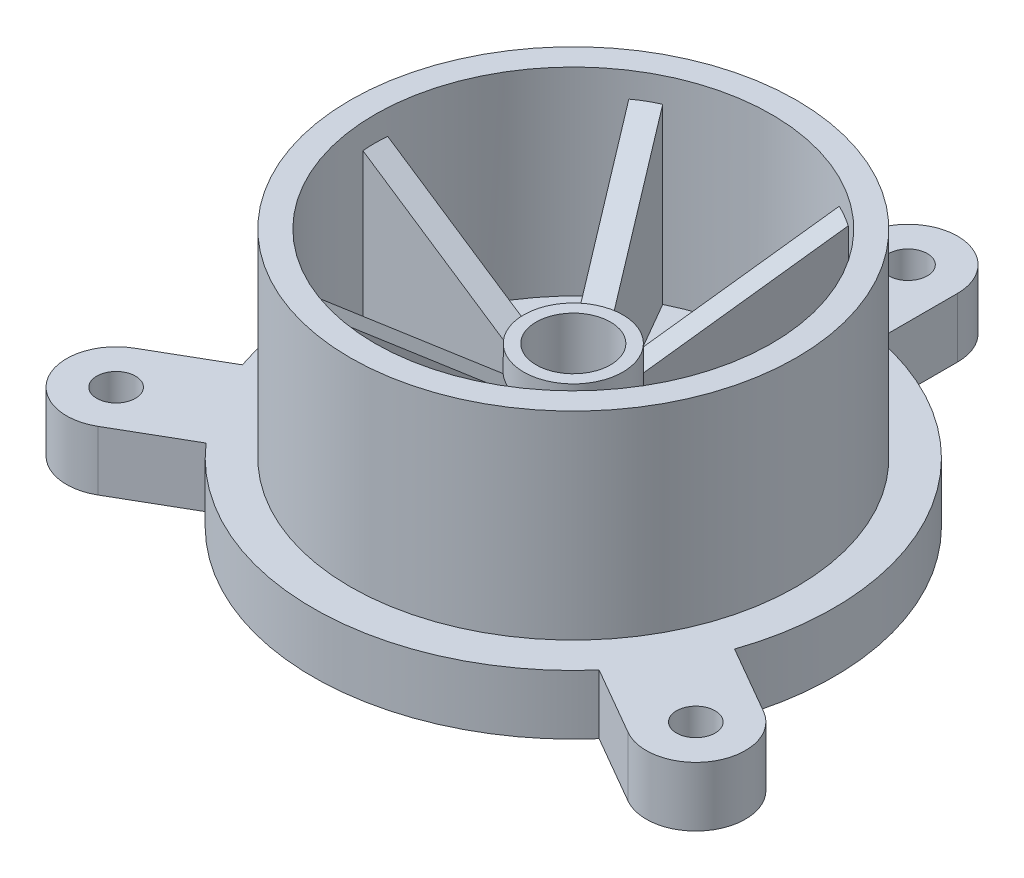
SolidWorks part; units mm, degrees
ref_plane "Front Plane" through (0, 0, 0) normal (0, 0, 1) x (1, 0, 0)
ref_plane "Top Plane" through (0, 0, 0) normal (0, 1, 0) x (1, 0, 0)
ref_plane "Right Plane" through (0, 0, 0) normal (1, 0, 0) x (0, 0, -1)
sketch "Sketch1" plane through (0, 0, 0) normal (0, 1, 0) x (1, 0, 0)
  line L0 (-10, 67.5) -> (-10, 51.5388)
  line L1 (10, 67.5) -> (10, 51.5388)
  line L2 (63.4567, -25.0897) -> (49.6339, -17.1092)
  line L3 (53.4567, -42.4103) -> (39.6339, -34.4297)
  line L4 (-53.4567, -42.4103) -> (-39.6339, -34.4297)
  line L5 (-63.4567, -25.0897) -> (-49.6339, -17.1092)
  arc A0 (-10, 51.5388) -> (-49.6339, -17.1092) centre (0, 0) ccw
  circle A1 centre (0, 0) radius 67.5 construction
  circle A2 centre (0, 67.5) radius 3.9
  arc A3 (9.9725, 66.7593) -> (-9.9725, 66.7593) centre (0, 67.5) ccw
  arc A4 (52.829, -42.0161) -> (62.8015, -24.7432) centre (58.4567, -33.75) ccw
  circle A5 centre (58.4567, -33.75) radius 3.9
  arc A6 (-62.8015, -24.7432) -> (-52.829, -42.0161) centre (-58.4567, -33.75) ccw
  circle A7 centre (-58.4567, -33.75) radius 3.9
  arc A8 (-39.6339, -34.4297) -> (39.6339, -34.4297) centre (0, 0) ccw
  arc A9 (49.6339, -17.1092) -> (10, 51.5388) centre (0, 0) ccw
  point P29 (0, 0)
  dimension "D1" = 105
  dimension "D2" = 135
  dimension "D3" = 20
  dimension "D4" = 7.8
  dimension "D5" = 3
extrude "Boss-Extrude1" add sketch "Sketch1" along normal blind 12 contours L2 A9 L1 A3 L0 A0 L5 A6 L4 A8 L3 A4 A2 A5 A7 region at (0, 0, 0)
sketch "Sketch2" plane through (0, 12, 0) normal (0, 1, 0) x (1, 0, 0)
  circle A0 centre (0, 0) radius 7.5
  dimension "D1" = 15
extrude "Cut-Extrude1" cut sketch "Sketch2" against normal blind 12
sketch "Sketch4" plane through (0, 12, 0) normal (0, 1, 0) x (1, 0, 0)
  circle A0 centre (0, 0) radius 10
  circle A1 centre (0, 0) radius 7.5 construction
  circle A2 centre (0, 0) radius 7.5
  dimension "D1" = 20
extrude "Boss-Extrude2" add sketch "Sketch4" along normal blind 20
sketch "Sketch5" plane through (0, 12, 0) normal (0, 1, 0) x (1, 0, 0)
  circle A0 centre (0, 0) radius 40
  circle A1 centre (0, 0) radius 45
  dimension "D1" = 90
  dimension "D2" = 80
extrude "Boss-Extrude3" add sketch "Sketch5" along normal blind 40
sketch "Sketch6" plane through (0, 0, 0) normal (0, 0, 1) x (1, 0, 0)
  line L0 (10, 27) -> (40, 47)
  line L1 (10, 12) -> (10, 32) construction
  line L2 (40, 12) -> (40, 52) construction
  line L3 (45, 52) -> (-45, 52) construction
  dimension "D1" = 5
  dimension "D2" = 5
rib "Rib1" sketch "Sketch6" sketch "Sketch6" thickness 5 extrusion direction parallel to sketch draft on no parameters "D1"=5
pattern_circular "CirPattern1" count 6 over 360 about axis through (0, 0, 0) along (0, 1, 0) of "Rib1"
